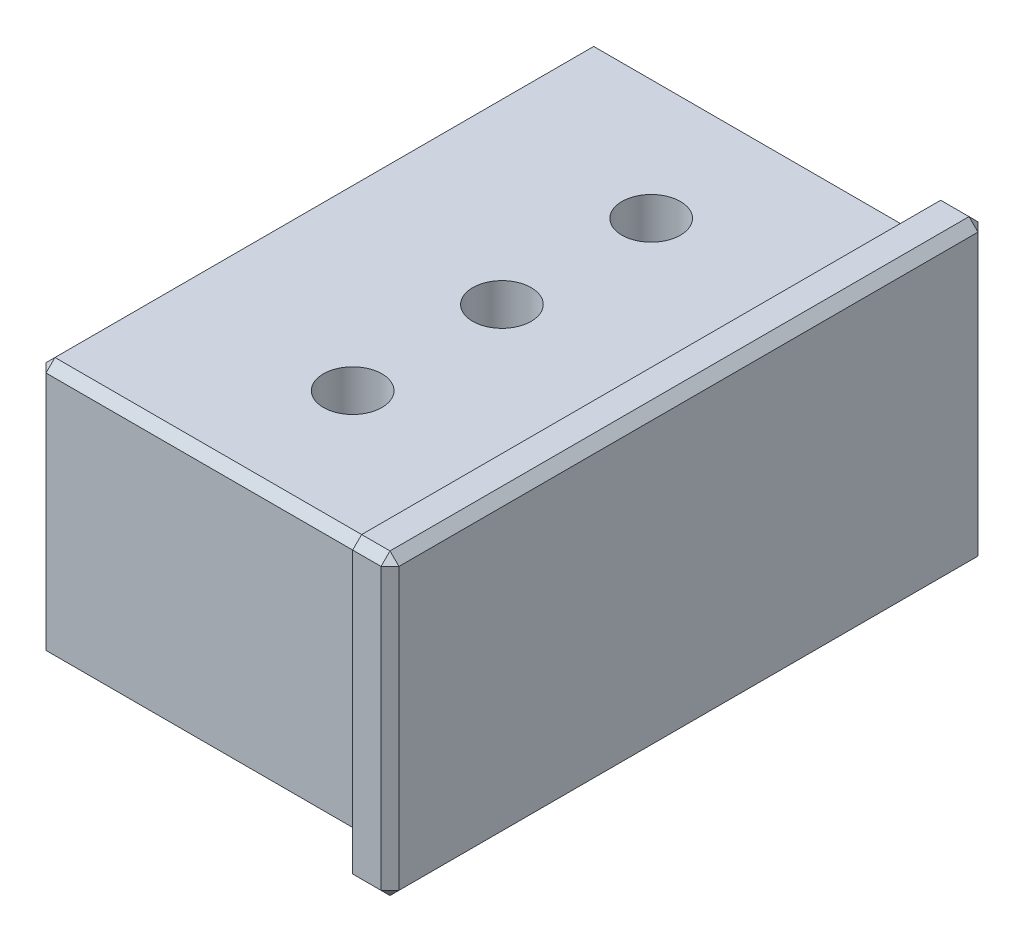
SolidWorks part; units mm, degrees
material "PET"
ref_plane "Front Plane" through (0, 0, 0) normal (0, 0, 1) x (1, 0, 0)
ref_plane "Top Plane" through (0, 0, 0) normal (0, 1, 0) x (1, 0, 0)
ref_plane "Right Plane" through (0, 0, 0) normal (1, 0, 0) x (0, 0, -1)
sketch "Sketch1" plane through (0, 0, 0) normal (1, 0, 0) x (0, 0, -1)
  line L1 (0, 0) -> (47.371, 0)
  line L2 (0, 0) -> (0, 21.971)
  line L3 (0, 21.971) -> (47.371, 21.971)
  line L4 (47.371, 0) -> (47.371, 21.971)
  dimension "D1" = 21.971
  dimension "D2" = 47.371
extrude "Boss-Extrude1" add sketch "Sketch1" along normal blind 28.575
sketch "Sketch2" plane through (28.575, 0, 0) normal (1, 0, 0) x (0, 0, -1)
  line L0 (0, 21.971) -> (47.371, 0) construction
  line L1 (0, 0) -> (47.371, 21.971) construction
  line L9 (49.0855, -1.7145) -> (-1.7145, -1.7145)
  line L10 (49.0855, -1.7145) -> (49.0855, 23.6855)
  line L11 (49.0855, 23.6855) -> (-1.7145, 23.6855)
  line L12 (-1.7145, -1.7145) -> (-1.7145, 23.6855)
  line L13 (49.0855, -1.7145) -> (-1.7145, 23.6855) construction
  line L14 (49.0855, 23.6855) -> (-1.7145, -1.7145) construction
  point P0 (23.6855, 10.9855)
  dimension "D1" = 50.8
  dimension "D2" = 25.4
extrude "Boss-Extrude2" add sketch "Sketch2" along normal blind 3.175
chamfer "Chamfer1" distance 0.762 angle 45 16 edges at (31.75, 23.6855, -23.6855) (30.1625, 23.6855, -49.0855) (31.75, 10.9855, -49.0855) (30.1625, -1.7145, -49.0855) (31.75, -1.7145, -23.6855) (30.1625, -1.7145, 1.7145) (31.75, 10.9855, 1.7145) (30.1625, 23.6855, 1.7145) (0, 0, -23.6855) (14.2875, 0, -47.371) (0, 10.9855, -47.371) (14.2875, 21.971, -47.371) (0, 21.971, -23.6855) (14.2875, 21.971, 0) (0, 10.9855, 0) (14.2875, 0, 0)
sketch "Sketch3" plane through (0, 21.971, 0) normal (0, 1, 0) x (1, 0, 0)
  circle A0 centre (15.875, 23.6855) radius 2.4892
  circle A1 centre (15.875, 36.3855) radius 2.4892
  circle A2 centre (15.875, 10.9855) radius 2.4892
  circle A3 centre (15.875, 36.3855) radius 2.4892 construction
  circle A4 centre (15.875, 10.9855) radius 2.4892 construction
  point P6 (0, 0)
  point P7 (0, 0)
  dimension "D1" = 4.9784
extrude "Cut-Extrude1" cut sketch "Sketch3" against normal through all
equation "\"D1@Sketch1\"=1-2*0.065-0.005"
equation "\"D2@Sketch1\"=2-2*0.065-0.005"
